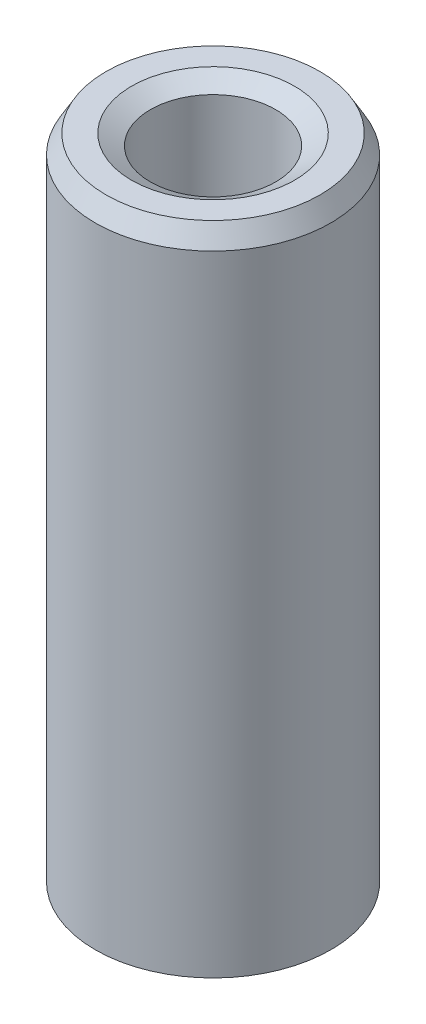
SolidWorks part; units mm, degrees
ref_plane "Front Plane" through (0, 0, 0) normal (0, 0, 1) x (1, 0, 0)
ref_plane "Top Plane" through (0, 0, 0) normal (0, 1, 0) x (1, 0, 0)
ref_plane "Right Plane" through (0, 0, 0) normal (1, 0, 0) x (0, 0, -1)
sketch "Sketch1" plane through (0, 0, 0) normal (0, 1, 0) x (1, 0, 0)
  circle A0 centre (0, 0) radius 17.5
  dimension "SLEEVE_OD" = 35
extrude "Boss-Extrude1" add sketch "Sketch1" along normal blind 97.9082
sketch "Sketch2" plane through (0, 0, 0) normal (0, 1, 0) x (1, 0, 0)
  circle A0 centre (0, 0) radius 9.3122
  dimension "BORE_D" = 18.6244
extrude "Cut-Extrude1" cut sketch "Sketch2" along normal through all
chamfer "Chamfer1" distance 2.7956 angle 30 4 edges at (0, 97.9082, 9.3122) (0, 0, 9.3122) (0, 0, 17.5) (0, 97.9082, 17.5) first distance on face at (0, 97.9082, 9.3122) first distance on face at (0, 0, 9.3122) first distance on face at (0, 97.9082, 17.5)
